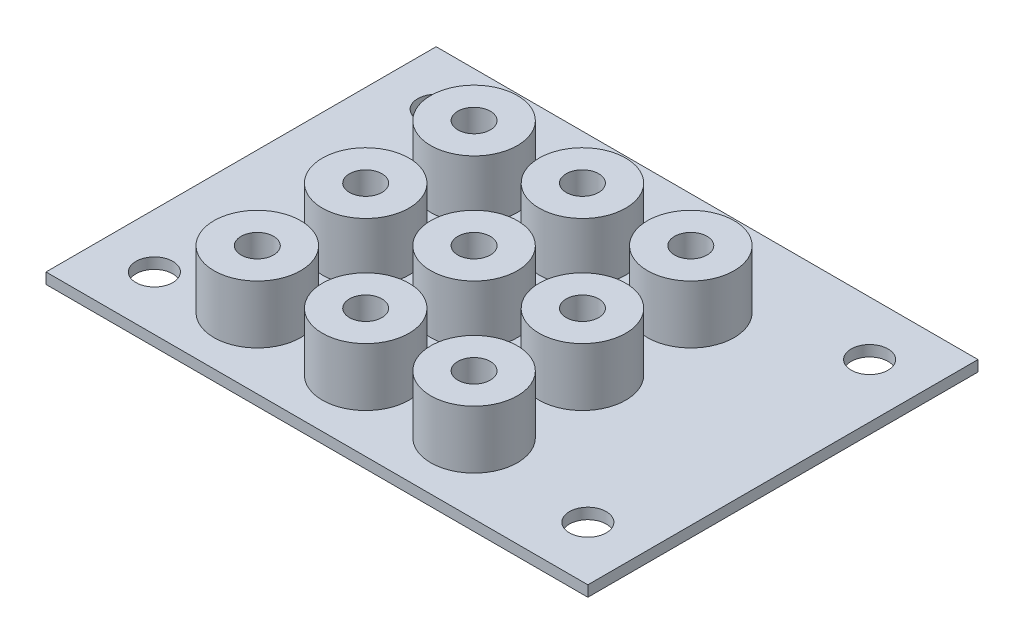
SolidWorks part; units mm, degrees
ref_plane "Front Plane" through (0, 0, 0) normal (0, 0, 1) x (1, 0, 0)
ref_plane "Top Plane" through (0, 0, 0) normal (0, 1, 0) x (1, 0, 0)
ref_plane "Right Plane" through (0, 0, 0) normal (1, 0, 0) x (0, 0, -1)
sketch "Sketch1" plane through (0, 0, 0) normal (0, 1, 0) x (1, 0, 0)
  line L0 (45, 31) -> (5, 31) construction
  line L1 (0, 0) -> (50, 0)
  line L2 (0, 0) -> (0, 36)
  line L3 (0, 36) -> (50, 36)
  line L4 (50, 0) -> (50, 36)
  line L6 (45, 31) -> (45, 5) construction
  circle A19 centre (13, 6.5) radius 1.25
  circle A28 centre (5, 5) radius 1.7
  circle A29 centre (5, 31) radius 1.7
  circle A30 centre (45, 31) radius 1.7
  circle A31 centre (45, 5) radius 1.7
  circle A32 centre (23, 6.5) radius 1.25
  circle A33 centre (33, 6.5) radius 1.25
  circle A34 centre (23, 16.5) radius 1.25
  circle A35 centre (33, 16.5) radius 1.25
  circle A36 centre (23, 26.5) radius 1.25
  circle A37 centre (33, 26.5) radius 1.25
  circle A38 centre (13, 16.5) radius 1.25
  circle A39 centre (13, 26.5) radius 1.25
  point P7 (45, 18)
  point P9 (25, 31)
  point P10 (25, 36)
  point P20 (50, 18)
  dimension "D5" = 40
  dimension "D6" = 26
  dimension "D3" = 2.5
  dimension "D8" = 3.4
  dimension "D1" = 50
  dimension "D2" = 36
  dimension "D4" = 8
  dimension "D7" = 1.5
  dimension "D9" = 3
extrude "Boss-Extrude1" add sketch "Sketch1" along normal blind 1 contours L1 L4 L3 L2 A39 A36 A34 region at (25.0514, 0, -18.0385)
sketch "Sketch2" plane through (0, 1, 0) normal (0, 1, 0) x (1, 0, 0)
  circle A0 centre (13, 26.5) radius 1.5
  circle A1 centre (13, 26.5) radius 1.25 construction
  circle A2 centre (13, 26.5) radius 4
  circle A3 centre (23, 26.5) radius 4
  circle A4 centre (23, 26.5) radius 1.5
  circle A5 centre (33, 26.5) radius 4
  circle A6 centre (33, 26.5) radius 1.5
  circle A7 centre (23, 16.5) radius 4
  circle A8 centre (23, 16.5) radius 1.5
  circle A9 centre (33, 16.5) radius 4
  circle A10 centre (33, 16.5) radius 1.5
  circle A11 centre (23, 6.5) radius 4
  circle A12 centre (23, 6.5) radius 1.5
  circle A13 centre (33, 6.5) radius 4
  circle A14 centre (33, 6.5) radius 1.5
  circle A15 centre (13, 16.5) radius 4
  circle A16 centre (13, 16.5) radius 1.5
  circle A17 centre (13, 6.5) radius 4
  circle A18 centre (13, 6.5) radius 1.5
  dimension "D1" = 3
  dimension "D2" = 8
extrude "Boss-Extrude2" add sketch "Sketch2" along normal blind 5.35
equation "\"o\"= 10mm"
equation "\"P\"= 10"
